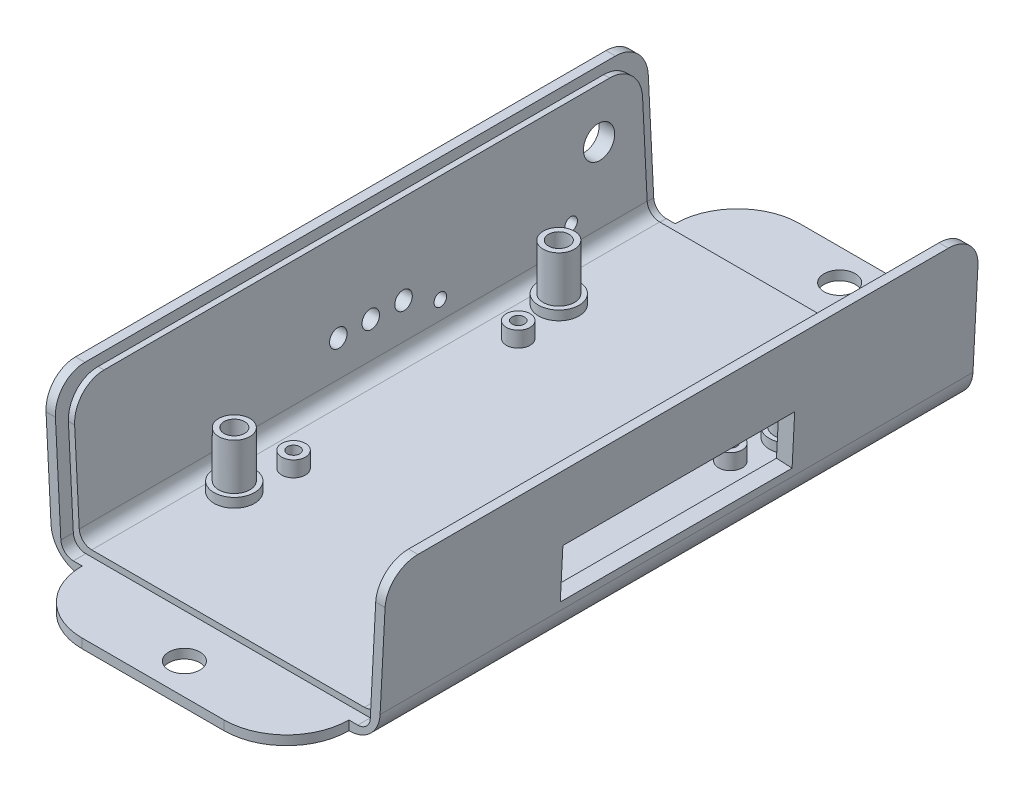
SolidWorks part; units mm, degrees
ref_plane "Front Plane" through (0, 0, 0) normal (0, 0, 1) x (1, 0, 0)
ref_plane "Top Plane" through (0, 0, 0) normal (0, 1, 0) x (1, 0, 0)
ref_plane "Right Plane" through (0, 0, 0) normal (1, 0, 0) x (0, 0, -1)
sketch "Sketch1" plane through (0, 0, 0) normal (0, 0, 1) x (1, 0, 0)
  line L0 (-26.1148, 0) -> (-27.425, 25)
  line L1 (-27.425, 25) -> (-24.9216, 25)
  line L2 (-24.9216, 25) -> (-23.7424, 2.5)
  line L3 (-23.7424, 2.5) -> (23.7424, 2.5)
  line L4 (23.7424, 2.5) -> (24.9216, 25)
  line L5 (24.9216, 25) -> (27.425, 25)
  line L6 (27.425, 25) -> (26.1148, 0)
  line L7 (26.1148, 0) -> (-26.1148, 0)
  line L8 (0, 0) -> (0, 5) construction
  point P2 (0, 0)
  point P12 (0, 2.5)
  dimension "D1" = 2.5
  dimension "D2" = 2.5
  dimension "D4" = 93
  dimension "D5" = 93
  dimension "D6" = 54.85
  dimension "D7" = 25
extrude "Boss-Extrude1" add sketch "Sketch1" along normal blind 95
sketch "Sketch2" plane through (23.5467, -1.234, 0) normal (-0.9986, 0.0523, 0) x (0, 0, 1)
  line L0 (93, 3.7392) -> (93, 24.8535)
  line L1 (95, 3.7392) -> (0, 3.7392) construction
  line L2 (93, 24.8535) -> (2, 24.8535)
  line L3 (2, 24.8535) -> (2, 3.7392)
  line L4 (2, 3.7392) -> (0, 3.7392)
  line L5 (0, 3.7392) -> (0, 26.8535)
  line L6 (0, 26.8535) -> (95, 26.8535)
  line L7 (95, 26.8535) -> (95, 3.7392)
  line L8 (95, 3.7392) -> (93, 3.7392)
  point P4 (0, 15.2963)
  dimension "D1" = 2
  dimension "D2" = 2
  dimension "D3" = 21.1143
  dimension "D4" = 2
extrude "Cut-Extrude1" cut sketch "Sketch2" against normal blind 1
sketch "Sketch4" plane through (-23.5467, -1.234, 0) normal (0.9986, 0.0523, 0) x (0, 0, -1)
  line L0 (-95, 3.7392) -> (-93, 3.7392)
  line L1 (-95, 3.7392) -> (0, 3.7392) construction
  line L2 (-93, 3.7392) -> (-93, 24.7546)
  line L3 (-93, 24.7546) -> (-2, 24.7546)
  line L4 (-2, 24.7546) -> (-2, 3.7392)
  line L5 (-2, 3.7392) -> (0, 3.7392)
  line L6 (0, 3.7392) -> (0, 26.7546)
  line L7 (0, 26.7546) -> (-95, 26.7546)
  line L8 (-95, 26.7546) -> (-95, 3.7392)
  line L10 (-95, 26.4011) -> (-95, 1.3667) construction
  dimension "D1" = 2
  dimension "D2" = 2
  dimension "D4" = 2
extrude "Cut-Extrude2" cut sketch "Sketch4" against normal blind 1
sketch "Sketch9" plane through (0, 0, 95) normal (0, 0, 1) x (1, 0, 0)
  line L0 (-24.741, 2.4477) -> (-24.6914, 1.5)
  line L1 (-24.6914, 1.5) -> (24.6914, 1.5)
  line L2 (24.6914, 1.5) -> (24.7438, 2.5)
  line L3 (24.741, 2.4477) -> (25.9229, 25) construction
  line L4 (24.7438, 2.5) -> (23.7424, 2.5)
  line L5 (23.7424, 2.5) -> (-23.7424, 2.5)
  line L6 (-23.7424, 2.5) -> (-24.7438, 2.5)
  line L7 (-24.741, 2.4477) -> (-25.8409, 23.4343) construction
  line L8 (-24.7438, 2.5) -> (-24.741, 2.4477)
  dimension "D1" = 1
extrude "Cut-Extrude4" cut sketch "Sketch9" against normal blind 2
sketch "Sketch10" plane through (0, 0, 0) normal (0, 0, -1) x (-1, 0, 0)
  line L0 (-24.741, 2.4477) -> (-24.6914, 1.5)
  line L1 (-24.6914, 1.5) -> (24.6914, 1.5)
  line L2 (24.6914, 1.5) -> (24.741, 2.4477)
  line L3 (24.741, 2.4477) -> (24.7438, 2.5)
  line L4 (25.8409, 23.4343) -> (24.741, 2.4477) construction
  line L5 (24.7438, 2.5) -> (23.7424, 2.5)
  line L6 (23.7424, 2.5) -> (-23.7424, 2.5)
  line L7 (-24.741, 2.4477) -> (-25.8461, 23.533) construction
  line L9 (-23.7424, 2.5) -> (-24.7438, 2.5)
  line L12 (-25.9229, 25) -> (-24.741, 2.4477) construction
  line L13 (-24.7438, 2.5) -> (-24.741, 2.4477)
  line L14 (24.741, 2.4477) -> (25.9229, 25) construction
  dimension "D1" = 1
extrude "Cut-Extrude5" cut sketch "Sketch10" against normal blind 2
fillet "Fillet1" radius 2 6 edges at (-23.7424, 2.5, 47.5) (23.7424, 2.5, 47.5) (24.6914, 1.5, 94) (-24.6914, 1.5, 94) (-24.6914, 1.5, 1) (24.6914, 1.5, 1)
fillet "Fillet2" radius 5 8 edges at (26.674, 25, 95) (-26.674, 25, 95) (-26.674, 25, 0) (26.674, 25, 0) (25.3467, 23.5592, 2) (-25.3416, 23.4605, 2) (-25.3416, 23.4605, 93) (25.3467, 23.5592, 93)
fillet "Fillet3" radius 5 2 edges at (-26.1148, 0, 47.5) (26.1148, 0, 47.5)
sketch "Sketch11" plane through (0, 2.5, 0) normal (0, 1, 0) x (1, 0, 0)
  line L0 (-91.1992, -47.5) -> (146.0492, -47.5) construction
  line L1 (27.425, -90) -> (27.425, -5) construction
  line L2 (-18.5, 3.4004) -> (-18.5, -115.9025) construction
  line L3 (18.5, -115.9025) -> (18.5, 21.1937) construction
  line L4 (0, 0) -> (0, -141.7854) construction
  line L5 (-17, 7.1529) -> (-17, -126.2544) construction
  line L6 (17, 7.1529) -> (17, -145.2651) construction
  line L7 (53.5862, -21.5) -> (-82.444, -21.5) construction
  line L8 (59.1547, -29.5) -> (-89.0069, -29.5) construction
  line L9 (53.5862, -73.5) -> (-111.2808, -73.5) construction
  line L10 (53.5862, -65.5) -> (-87.6147, -65.5) construction
  circle A0 centre (-18.5, -21.5) radius 3.25
  circle A1 centre (18.5, -21.5) radius 3.25
  circle A2 centre (-17, -29.5) radius 1.9
  circle A3 centre (17, -29.5) radius 1.9
  circle A4 centre (18.5, -73.5) radius 3.25
  circle A5 centre (17, -65.5) radius 1.9
  circle A6 centre (-18.5, -73.5) radius 3.25
  circle A7 centre (-17, -65.5) radius 1.9
  point P8 (27.425, -47.5)
  dimension "D9" = 6.5
  dimension "D10" = 3.8
  dimension "D1" = 18.5
  dimension "D2" = 18.5
  dimension "D3" = 17
  dimension "D4" = 17
  dimension "D5" = 26
  dimension "D6" = 26
  dimension "D7" = 18
  dimension "D8" = 18
extrude "Boss-Extrude2" add sketch "Sketch11" along normal blind 1.5
sketch "Sketch13" plane through (0, 4, 0) normal (0, 1, 0) x (1, 0, 0)
  circle A0 centre (-18.5, -21.5) radius 2.5
  circle A1 centre (18.5, -21.5) radius 2.5
  circle A6 centre (-18.5, -73.5) radius 2.5
  circle A7 centre (18.5, -73.5) radius 2.5
  dimension "D1" = 5
extrude "Boss-Extrude3" add sketch "Sketch13" along normal blind 7.4
sketch "Sketch14" plane through (0, 4, 0) normal (0, 1, 0) x (1, 0, 0)
  circle A0 centre (-17, -29.5) radius 1.9
  circle A1 centre (17, -29.5) radius 1.9
  circle A2 centre (-17, -65.5) radius 1.9
  circle A3 centre (17, -65.5) radius 1.9
extrude "Boss-Extrude4" add sketch "Sketch14" along normal blind 1
sketch "Sketch15" plane through (0, 11.4, 0) normal (0, 1, 0) x (1, 0, 0)
  circle A0 centre (-18.5, -21.5) radius 1.65
  circle A1 centre (18.5, -21.5) radius 1.65
  circle A2 centre (18.5, -73.5) radius 1.65
  circle A3 centre (-18.5, -73.5) radius 1.65
  dimension "D1" = 3.3
extrude "Cut-Extrude7" cut sketch "Sketch15" against normal blind 15
sketch "Sketch16" plane through (0, 0, 0) normal (0, -1, 0) x (1, 0, 0)
  circle A0 centre (18.5, 21.5) radius 2.75
  circle A1 centre (-18.5, 21.5) radius 2.75
  circle A2 centre (18.5, 73.5) radius 2.75
  circle A3 centre (-18.5, 73.5) radius 2.75
  dimension "D1" = 5.5
extrude "Cut-Extrude8" cut sketch "Sketch16" against normal blind 1
sketch "Sketch17" plane through (0, 5, 0) normal (0, 1, 0) x (1, 0, 0)
  circle A0 centre (-17, -29.5) radius 1
  circle A1 centre (-17, -65.5) radius 1
  circle A2 centre (17, -65.5) radius 1
  circle A3 centre (17, -29.5) radius 1
  dimension "D1" = 2
extrude "Cut-Extrude9" cut sketch "Sketch17" against normal blind 2
sketch "Sketch18" plane through (26.0433, -1.3649, 0) normal (0.9986, -0.0523, 0) x (0, 0, -1)
  line L1 (-66.1959, 15.4337) -> (-29.0517, 15.4337)
  line L2 (-66.1959, 15.4337) -> (-66.1959, 7.3747)
  line L3 (-66.1959, 7.3747) -> (-29.0517, 7.3747)
  line L4 (-29.0517, 15.4337) -> (-29.0517, 7.3747)
extrude "Cut-Extrude10" cut sketch "Sketch18" against normal blind 3
sketch "Sketch19" plane through (-26.0433, -1.3649, 0) normal (-0.9986, -0.0523, 0) x (0, 0, 1)
  line L0 (40.7492, 11.1116) -> (51.3632, 11.1116) construction
  line L1 (14.0345, 8.4116) -> (34.9992, 8.4116) construction
  line L2 (0, 21.3942) -> (0, 6.1116) construction
  line L3 (0, 6.1116) -> (95, 6.1116) construction
  circle A0 centre (14.0345, 8.4116) radius 1
  circle A2 centre (34.9992, 8.4116) radius 1
  circle A3 centre (40.7492, 11.1116) radius 1.4
  circle A4 centre (45.9992, 11.1116) radius 1.4
  circle A5 centre (51.1992, 11.1116) radius 1.4
  point P23 (47.5, 6.1116)
  dimension "D1" = 2
  dimension "D4" = 11
  dimension "D12" = 2.8
  dimension "D13" = 5.25
  dimension "D8" = 2.8
  dimension "D9" = 5.2
  dimension "D2" = 2.3
  dimension "D3" = 5
  dimension "D7" = 14.0345
extrude "Cut-Extrude11" cut sketch "Sketch19" against normal blind 3
sketch "Sketch20" plane through (0, 0, 0) normal (0, 0, -1) x (-1, 0, 0)
  line L0 (-22.7934, 1.5) -> (22.7934, 1.5) construction
  line L1 (-21.37, 0) -> (21.37, 0)
  line L2 (-21.37, 0) -> (-21.37, 1.5)
  line L3 (-21.37, 1.5) -> (21.37, 1.5)
  line L4 (21.37, 0) -> (21.37, 1.5)
extrude "Boss-Extrude5" add sketch "Sketch20" along normal blind 10
fillet "Fillet4" radius 10 2 edges at (21.37, 0.75, -10) (-21.37, 0.75, -10)
sketch "Sketch21" plane through (0, 0, 95) normal (0, 0, 1) x (1, 0, 0)
  line L0 (-22.7934, 1.5) -> (22.7934, 1.5) construction
  line L1 (-21.37, 0) -> (21.37, 0)
  line L2 (-21.37, 0) -> (-21.37, 1.5)
  line L3 (-21.37, 1.5) -> (21.37, 1.5)
  line L4 (21.37, 0) -> (21.37, 1.5)
extrude "Boss-Extrude6" add sketch "Sketch21" along normal blind 10
fillet "Fillet5" radius 10 2 edges at (-21.37, 0.75, 105) (21.37, 0.75, 105)
sketch "Sketch22" plane through (0, 1.5, 0) normal (0, 1, 0) x (1, 0, 0)
  line L0 (0, 10) -> (0, -112.7156) construction
  line L1 (-11.37, 10) -> (11.37, 10) construction
  line L2 (11.37, -105) -> (-11.37, -105) construction
  circle A0 centre (0, 5) radius 2.5
  circle A1 centre (0, -100) radius 2.5
  dimension "D1" = 5
  dimension "D2" = 5
  dimension "D3" = 5
extrude "Cut-Extrude12" cut sketch "Sketch22" against normal blind 10
sketch "Sketch23" plane through (-26.0433, -1.3649, 0) normal (-0.9986, -0.0523, 0) x (0, 0, 1)
  line L0 (0, 17.1116) -> (29.0826, 17.1116) construction
  line L1 (0, 21.3942) -> (0, 6.1116) construction
  line L2 (0, 6.1116) -> (95, 6.1116) construction
  circle A0 centre (9.1042, 17.1116) radius 2.5
  dimension "D4" = 5
  dimension "D1" = 11
  dimension "D2" = 9.1042
extrude "Cut-Extrude13" cut sketch "Sketch23" against normal blind 4.5
